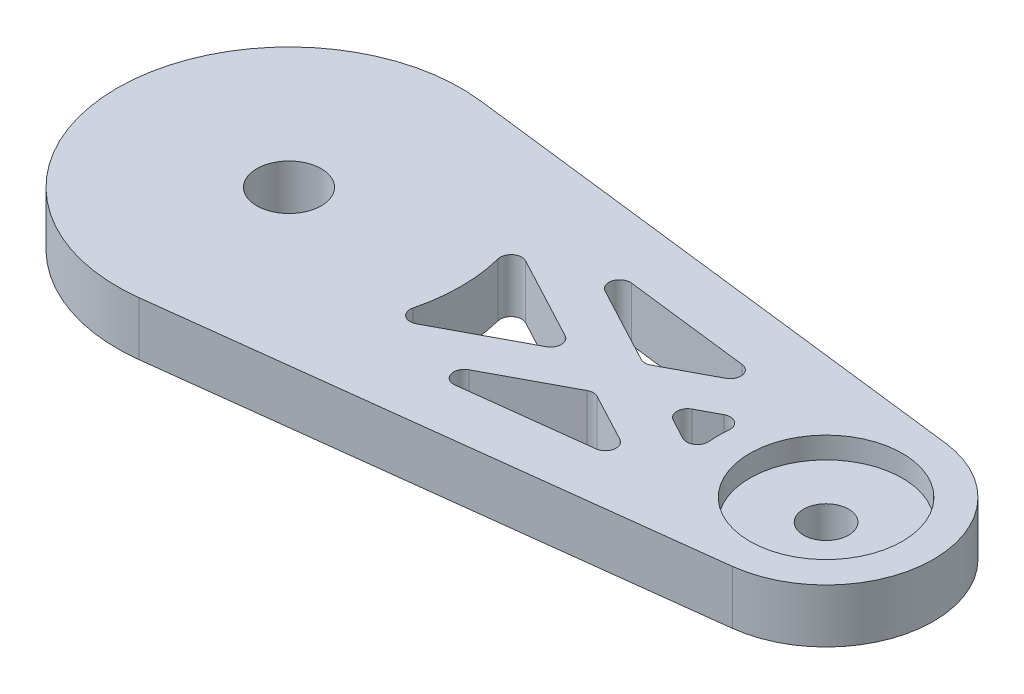
SolidWorks part; units mm, degrees
material "三聚氰胺甲醛树脂"
ref_plane "前视基准面" through (0, 0, 0) normal (0, 0, 1) x (1, 0, 0)
ref_plane "上视基准面" through (0, 0, 0) normal (0, 1, 0) x (1, 0, 0)
ref_plane "右视基准面" through (0, 0, 0) normal (1, 0, 0) x (0, 0, -1)
sketch "草图1" plane through (0, 0, 0) normal (0, 1, 0) x (1, 0, 0)
  line L0 (0, 0) -> (-5.9584, 0) construction
  line L1 (1.92, -15.8844) -> (51.2, -9.9277)
  line L2 (1.92, 15.8844) -> (51.2, 9.9277)
  line L3 (18.3565, 8.8613) -> (38.5355, 6.4222)
  line L4 (18.3565, -8.8613) -> (38.5355, -6.4222)
  line L5 (12.855, 9.5262) -> (42.0023, -6.0031) construction
  line L6 (12.855, -9.5262) -> (42.0023, 6.0031) construction
  line L7 (14.7223, 6.2652) -> (26.4816, 0)
  line L8 (18.3565, 8.8613) -> (30.735, 2.2662)
  line L9 (14.7223, -6.2652) -> (26.4816, 0)
  line L10 (18.3565, -8.8613) -> (30.735, -2.2662)
  line L11 (30.735, 2.2662) -> (38.5355, 6.4222)
  line L12 (34.9884, 0) -> (40.4294, -2.8989)
  line L13 (34.9884, 0) -> (40.4294, 2.8989)
  line L14 (30.735, -2.2662) -> (38.5355, -6.4222)
  circle A0 centre (0, 0) radius 12 construction
  arc A5 (1.92, 15.8844) -> (1.92, -15.8844) centre (0, 0) ccw
  arc A7 (40.4294, 2.8989) -> (40.4294, -2.8989) centre (50, 0) ccw
  circle A8 centre (50, 0) radius 2.1
  circle A9 centre (50, 0) radius 7.1
  arc A10 (14.7223, -6.2652) -> (14.7223, 6.2652) centre (0, 0) ccw
  circle A11 centre (0, 0) radius 16 construction
  arc A12 (51.2, -9.9277) -> (51.2, 9.9277) centre (50, 0) ccw
  circle A13 centre (50, 0) radius 10 construction
  circle A14 centre (0, 0) radius 3
  point P15 (0, 0)
  dimension "D1" = 24
  dimension "D2" = 6
  dimension "D4" = 20
  dimension "D5" = 32
  dimension "D7" = 4.2
  dimension "D8" = 14.2
  dimension "D3" = 50
  dimension "D9" = 5
  dimension "D10" = 5
  dimension "D11" = 2
  dimension "D12" = 2
  dimension "D13" = 2
  dimension "D14" = 2
extrude "凸台-拉伸1" add sketch "草图1" along normal blind 5 contours L1 A7 L2 A5 A9 region at (15.5364, 0, 0)
extrude "凸台-拉伸2" add sketch "草图1<3>" along normal blind 3 contours A9 A8 region at (43.1008, 0, 0)
sketch "草图1<3>" plane through (0, 0, 0) normal (0, 1, 0) x (1, 0, 0) same geometry as "草图1"
fillet "圆角1" radius 1 3 edges at (34.9884, 2.5, 0) (40.4294, 2.5, -2.8989) (40.4294, 2.5, 2.8989)
fillet "圆角2" radius 1 3 edges at (30.735, 2.5, 2.2662) (18.3565, 2.5, 8.8613) (38.5355, 2.5, 6.4222)
fillet "圆角3" radius 1 3 edges at (18.3565, 2.5, -8.8613) (30.735, 2.5, -2.2662) (38.5355, 2.5, -6.4222)
fillet "圆角4" radius 1 3 edges at (14.7223, 2.5, -6.2652) (26.4816, 2.5, 0) (14.7223, 2.5, 6.2652)
